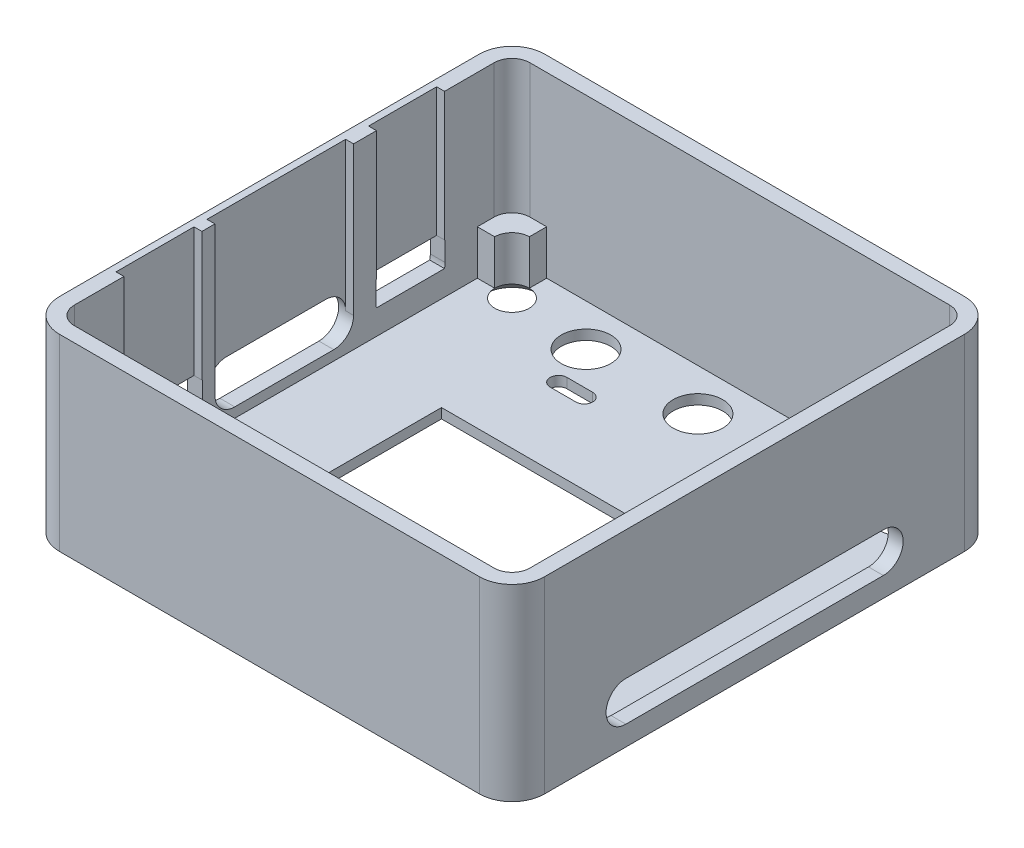
SolidWorks part; units mm, degrees
note: The reader was unsure of these and kept them because the rebuilt part matched: shared geometry of "草图1<3>".
ref_plane "前视基准面" through (0, 0, 0) normal (0, 0, 1) x (1, 0, 0)
ref_plane "上视基准面" through (0, 0, 0) normal (0, 1, 0) x (1, 0, 0)
ref_plane "右视基准面" through (0, 0, 0) normal (1, 0, 0) x (0, 0, -1)
other "Configuration Table"
sketch "草图1" plane through (0, 0, 0) normal (0, 1, 0) x (1, 0, 0)
  line L1 (-21.2, -23) -> (21.2, -23)
  line L2 (-23, -21.2) -> (-23, 21.2)
  line L3 (-21.2, 23) -> (21.2, 23)
  line L4 (23, -21.2) -> (23, 21.2)
  line L5 (-23, -23) -> (23, 23) construction
  line L6 (-23, 23) -> (23, -23) construction
  arc A0 (21.2, 23) -> (23, 21.2) centre (21.2, 21.2) cw
  arc A1 (23, -21.2) -> (21.2, -23) centre (21.2, -21.2) cw
  arc A2 (-21.2, -23) -> (-23, -21.2) centre (-21.2, -21.2) cw
  arc A3 (-23, 21.2) -> (-21.2, 23) centre (-21.2, 21.2) cw
  circle A4 centre (-19.5, 19.5) radius 1.75
  circle A5 centre (19.5, 19.5) radius 1.75
  circle A6 centre (19.5, -19.5) radius 1.75
  circle A7 centre (-19.5, -19.5) radius 1.75
  point P0 (0, 0)
  point P29 (0, 0)
  dimension "D3" = 1.8
  dimension "D5" = 3.5
  dimension "D1" = 46
  dimension "D2" = 46
  dimension "D4" = 3.5
  dimension "D6" = 4
extrude "拉伸-薄壁1" add sketch "草图1" along normal blind 19 thin contours A3 L2 A2 L1 A1 L4 A0 L3 A7 A6 A5 A4 | A5 | A6 | A7 | A4
extrude "凸台-拉伸1" add sketch "草图1<3>" along normal blind 1
sketch "草图1<3>" plane through (0, 0, 0) normal (0, 1, 0) x (1, 0, 0) same geometry as "草图1"
hole_wizard "M2.5 平头机械螺钉的锥形沉头孔1" positions "3D草图1" profile "草图2" countersink size "M2.5" standard "ANSI Metric"
sketch3d "3D草图1"
  line L0 (-19.5, 1, 19.5) -> (-19.5, 0, 19.5) construction
  line L1 (19.5, 1, 19.5) -> (19.5, 0, 19.5) construction
  line L2 (19.5, 1, -19.5) -> (19.5, 0, -19.5) construction
  line L3 (-19.5, 1, -19.5) -> (-19.5, 0, -19.5) construction
  point P0 (-19.5, 0, 19.5)
  point P4 (19.5, 0, 19.5)
  point P8 (19.5, 0, -19.5)
  point P12 (-19.5, 0, -19.5)
sketch "草图2" plane through (-19.5, 0, 19.5) normal (1, 0, 0) x (0, 0, -1)
  line L0 (0, 0) -> (0, 10.9313)
  line L1 (0, 10.9313) -> (1.55, 10)
  line L2 (1.55, 10) -> (1.55, 1.2)
  line L3 (1.55, 1.2) -> (2.75, 0)
  line L5 (2.75, 0) -> (0, 0)
  line L6 (-1.55, 1.2) -> (-2.75, 0) construction
  line L10 (0, 10.9313) -> (-1.55, 10) construction
  line L11 (0, -6.35) -> (0, 107.95) construction
  dimension "孔直径" = 3.1
  dimension "孔深度" = 10
  dimension "近端锥形沉头孔直径" = 5.5
  dimension "近端锥形沉头孔角度" = 90
  dimension "导头角度" = 118
sketch "草图4" plane through (0, 0, 0) normal (0, -1, 0) x (1, 0, 0)
  line L5 (-13.5, 20.1327) -> (13.5, 20.1327)
  line L6 (-13.5, 20.1327) -> (-13.5, -6.3802)
  line L7 (-13.5, -6.3802) -> (13.5, -6.3802)
  line L8 (13.5, 20.1327) -> (13.5, -6.3802)
  line L11 (7.2, -14.5) -> (9.8, -14.5) construction
  line L12 (7.2, -13.65) -> (9.8, -13.65)
  line L13 (7.2, -15.35) -> (9.8, -15.35)
  line L14 (-9.8, -14.5) -> (-7.2, -14.5) construction
  line L15 (-9.8, -13.65) -> (-7.2, -13.65)
  line L16 (-9.8, -15.35) -> (-7.2, -15.35)
  line L18 (-24.5, 21.2) -> (-24.5, -21.2) construction
  line L19 (24.5, 21.2) -> (24.5, -21.2) construction
  circle A0 centre (-11.3, -18.775) radius 2.5
  circle A1 centre (0, -18.775) radius 2.5
  circle A2 centre (12.3, -18.775) radius 2.5
  arc A7 (7.2, -13.65) -> (7.2, -15.35) centre (7.2, -14.5) ccw
  arc A8 (9.8, -15.35) -> (9.8, -13.65) centre (9.8, -14.5) ccw
  arc A9 (-9.8, -13.65) -> (-9.8, -15.35) centre (-9.8, -14.5) ccw
  arc A10 (-7.2, -15.35) -> (-7.2, -13.65) centre (-7.2, -14.5) ccw
  circle A11 centre (-19.5, -19.5) radius 1.75 construction
  circle A12 centre (-19.5, -19.5) radius 1.75
  point P21 (0, -6.3802)
  point P22 (8.5, -14.5)
  point P29 (-8.5, -14.5)
  dimension "D1" = 5
  dimension "D2" = 16
  dimension "D3" = 5
  dimension "D4" = 11.3
  dimension "D5" = 12.3
  dimension "D6" = 0.725
  dimension "D7" = 16
  dimension "D14" = 27
  dimension "D15" = 26.5129
extrude "切除-拉伸1" cut sketch "草图4" against normal blind 143
sketch "草图5" plane through (-24.5, 0, 0) normal (-1, 0, 0) x (0, 0, 1)
  line L0 (14.25, 4) -> (-14.25, 4) construction
  line L1 (14.25, 2) -> (-14.25, 2)
  line L2 (14.25, 6) -> (-14.25, 6)
  line L3 (-14.25, 4) -> (-11.25, 4) construction
  line L4 (21.2, 0) -> (-21.2, 0) construction
  line L5 (-14.25, 6) -> (-11.25, 6)
  line L6 (-14.25, 2) -> (-11.25, 2)
  line L7 (-5, 4) -> (5, 4) construction
  line L8 (-5, 6) -> (5, 6)
  line L9 (-5, 2) -> (5, 2)
  line L10 (14.25, 4) -> (10.25, 4) construction
  line L11 (14.25, 2) -> (10.25, 2)
  line L12 (14.25, 6) -> (10.25, 6)
  line L13 (-9.25, 6) -> (-9.25, 3.5)
  line L14 (-16.25, 6) -> (16.25, 6)
  line L15 (-16.25, 6) -> (-16.25, 3.5)
  line L16 (-16.25, 3.5) -> (16.25, 3.5)
  line L17 (16.25, 6) -> (16.25, 3.5)
  line L18 (8.25, 6) -> (8.25, 3.5)
  arc A0 (14.25, 2) -> (14.25, 6) centre (14.25, 4) ccw
  arc A1 (-14.25, 6) -> (-14.25, 2) centre (-14.25, 4) ccw
  arc A2 (-14.25, 6) -> (-14.25, 2) centre (-14.25, 4) ccw
  arc A3 (-11.25, 2) -> (-11.25, 6) centre (-11.25, 4) ccw
  arc A4 (-5, 6) -> (-5, 2) centre (-5, 4) ccw
  arc A5 (5, 2) -> (5, 6) centre (5, 4) ccw
  arc A6 (14.25, 2) -> (14.25, 6) centre (14.25, 4) ccw
  arc A7 (10.25, 6) -> (10.25, 2) centre (10.25, 4) ccw
  point P2 (0, 4)
  point P11 (-12.75, 4)
  point P19 (0, 4)
  point P26 (12.25, 4)
  dimension "D2" = 28.5
  dimension "D1" = 4
  dimension "D3" = 4
  dimension "D4" = 4
  dimension "D5" = 3
  dimension "D6" = 4
  dimension "D7" = 5
  dimension "D8" = 5
  dimension "D9" = 4
  dimension "D10" = 4
  dimension "D11" = 2.5
  dimension "D12" = 0
extrude "切除-拉伸2" cut sketch "草图5" against normal blind 21 contours L16 A3 L2 A1 | L16 A5 L2 A4 | L1 A5 L16 A4 | L2 A7 L16 A0 | A1 L14 L15 | A0 L17 L14 | A3 L13 L2 | A7 L2 L18
sketch "草图7" plane through (24.5, 0, 0) normal (1, 0, 0) x (0, 0, -1)
  line L0 (-13, 4) -> (13, 4) construction
  line L1 (-13, 6) -> (13, 6)
  line L2 (-13, 2) -> (13, 2)
  line L3 (-21.2, 0) -> (21.2, 0) construction
  arc A0 (-13, 6) -> (-13, 2) centre (-13, 4) ccw
  arc A1 (13, 2) -> (13, 6) centre (13, 4) ccw
  point P2 (0, 4)
  dimension "D1" = 4
  dimension "D2" = 4
  dimension "D3" = 26
extrude "切除-拉伸4" cut sketch "草图7" against normal blind 27
sketch "草图8" plane through (0, 1, 0) normal (0, 1, 0) x (1, 0, 0)
  line L0 (-21.25, 19.5) -> (-23, 19.5)
  line L1 (-19.5, 21.25) -> (-19.5, 23)
  line L2 (21.25, 19.5) -> (23, 19.5)
  line L3 (19.5, 21.25) -> (19.5, 23)
  line L4 (21.2, 23) -> (-21.2, 23)
  line L5 (-23, 21.2) -> (-23, -21.2)
  line L6 (-21.2, -23) -> (21.2, -23)
  line L7 (23, -21.2) -> (23, 21.2)
  line L8 (21.2, 23) -> (-21.2, 23)
  line L9 (-23, 21.2) -> (-23, -21.2)
  line L10 (-21.2, -23) -> (21.2, -23)
  line L11 (23, -21.2) -> (23, 21.2)
  line L12 (19.5, -21.25) -> (19.5, -23)
  line L13 (21.25, -19.5) -> (23, -19.5)
  line L14 (-21.25, -19.5) -> (-23, -19.5)
  line L15 (-19.5, -21.25) -> (-19.5, -23)
  circle A0 centre (-19.5, 19.5) radius 1.75 construction
  circle A1 centre (-19.5, -19.5) radius 1.75 construction
  circle A2 centre (19.5, -19.5) radius 1.75 construction
  circle A3 centre (19.5, 19.5) radius 1.75 construction
  arc A4 (23, 21.2) -> (21.2, 23) centre (21.2, 21.2) ccw
  arc A5 (-21.2, 23) -> (-23, 21.2) centre (-21.2, 21.2) ccw
  arc A6 (-23, -21.2) -> (-21.2, -23) centre (-21.2, -21.2) ccw
  arc A7 (21.2, -23) -> (23, -21.2) centre (21.2, -21.2) ccw
  arc A8 (23, 21.2) -> (21.2, 23) centre (21.2, 21.2) ccw
  arc A9 (-21.2, 23) -> (-23, 21.2) centre (-21.2, 21.2) ccw
  arc A10 (-23, -21.2) -> (-21.2, -23) centre (-21.2, -21.2) ccw
  arc A11 (21.2, -23) -> (23, -21.2) centre (21.2, -21.2) ccw
  circle A12 centre (-19.5, -19.5) radius 1.75
  circle A13 centre (19.5, -19.5) radius 1.75
  circle A14 centre (19.5, 19.5) radius 1.75
  circle A15 centre (-19.5, 19.5) radius 1.75
  point P34 (0, 0)
  arc M36 (23, 21.2) -> (21.2, 23) centre (21.2, 21.2) ccw
  line M37 (21.2, 23) -> (-21.2, 23)
  arc M38 (-21.2, 23) -> (-23, 21.2) centre (-21.2, 21.2) ccw
  line M39 (-23, 21.2) -> (-23, -21.2)
  arc M40 (-23, -21.2) -> (-21.2, -23) centre (-21.2, -21.2) ccw
  line M41 (-21.2, -23) -> (21.2, -23)
  arc M42 (21.2, -23) -> (23, -21.2) centre (21.2, -21.2) ccw
  line M43 (23, -21.2) -> (23, 21.2)
  circle M44 centre (-19.5, 19.5) radius 1.75
  circle M45 centre (19.5, 19.5) radius 1.75
  circle M46 centre (19.5, -19.5) radius 1.75
  circle M47 centre (-19.5, -19.5) radius 1.75
  dimension "D1" = 0
  dimension "D2" = 4
extrude "凸台-拉伸2" add sketch "草图8" along normal blind 4.5 contours L1 L0 M44 M37 M38 M39 | L15 L14 L9 M47 M40 M41 | L13 L12 L10 M46 M42 M43 | L3 L2 M45 M43 M36 M37
sketch "草图9" plane through (-23, 0, 0) normal (1, 0, 0) x (0, 0, -1)
  line L0 (-7, 4) -> (-7, 19)
  line L1 (-21.2, 19) -> (21.2, 19) construction
  line L2 (7, 4) -> (7, 19)
  line L3 (7, 19) -> (-7, 19)
  line L4 (-8.3135, 3.5) -> (-8.3135, 19)
  line L5 (-16.1865, 3.5) -> (-16.1865, 19)
  line L6 (9.3135, 3.5) -> (9.3135, 19)
  line L7 (16.1865, 3.5) -> (16.1865, 19)
  line L8 (11.25, 6) -> (14.25, 6) construction
  line L9 (-5, 6) -> (5, 6) construction
  line L10 (-14.25, 6) -> (-10.25, 6) construction
  line L11 (11.25, 6) -> (14.25, 6)
  line L12 (-5, 6) -> (5, 6)
  line L13 (-14.25, 6) -> (-10.25, 6)
  arc A0 (-5, 6) -> (-5, 2) centre (-5, 4) ccw construction
  arc A1 (5, 2) -> (5, 6) centre (5, 4) ccw construction
  arc A2 (16.1865, 3.5) -> (14.25, 6) centre (14.25, 4) ccw construction
  arc A3 (11.25, 6) -> (9.3135, 3.5) centre (11.25, 4) ccw construction
  arc A4 (-8.3135, 3.5) -> (-10.25, 6) centre (-10.25, 4) ccw construction
  arc A5 (-14.25, 6) -> (-16.1865, 3.5) centre (-14.25, 4) ccw construction
  arc A6 (16.1865, 3.5) -> (14.25, 6) centre (14.25, 4) ccw
  arc A7 (11.25, 6) -> (9.3135, 3.5) centre (11.25, 4) ccw
  arc A8 (5, 2) -> (5, 6) centre (5, 4) ccw
  arc A9 (-5, 6) -> (-5, 2) centre (-5, 4) ccw
  arc A10 (-8.3135, 3.5) -> (-10.25, 6) centre (-10.25, 4) ccw
  arc A11 (-14.25, 6) -> (-16.1865, 3.5) centre (-14.25, 4) ccw
extrude "切除-拉伸5" cut sketch "草图9" against normal blind 0.8
